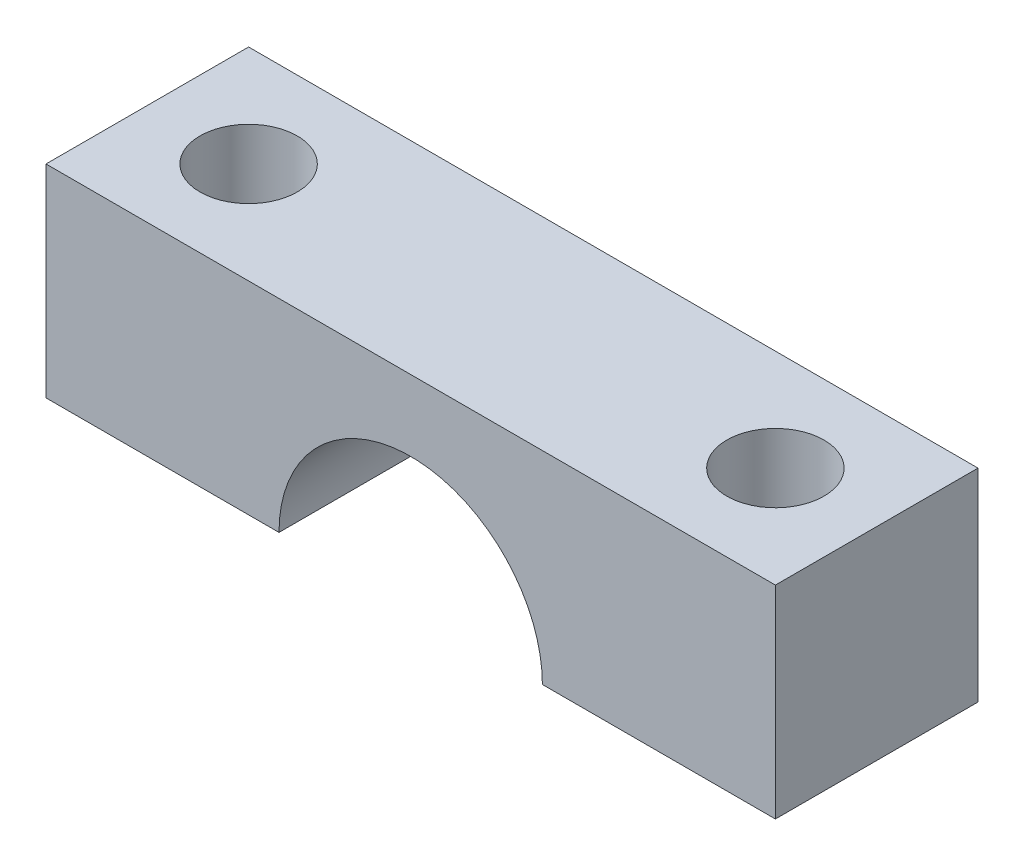
SolidWorks part; units mm, degrees
ref_plane "Front Plane" through (0, 0, 0) normal (0, 0, 1) x (1, 0, 0)
ref_plane "Top Plane" through (0, 0, 0) normal (0, 1, 0) x (1, 0, 0)
ref_plane "Right Plane" through (0, 0, 0) normal (1, 0, 0) x (0, 0, -1)
sketch "Sketch1" plane through (0, 0, 0) normal (0, 0, 1) x (1, 0, 0)
  line L0 (0, 0) -> (0, 5) construction
  line L1 (3.25, 0) -> (9, 0)
  line L2 (9, 0) -> (9, 5)
  line L3 (9, 5) -> (-9, 5)
  line L4 (-9, 0) -> (-9, 5)
  line L5 (-3.25, 0) -> (-9, 0)
  arc A0 (3.25, 0) -> (-3.25, 0) centre (0, 0) ccw
  dimension "D3" = 3.25
  dimension "D1" = 18
  dimension "D2" = 5
extrude "Boss-Extrude1" add sketch "Sketch1" along normal blind 5
sketch "Sketch2" plane through (0, 0, 0) normal (0, 1, 0) x (1, 0, 0)
  line L0 (0, 0) -> (0, -5) construction
  line L1 (9, 0) -> (-9, 0) construction
  line L2 (9, -5) -> (-9, -5) construction
  line L3 (-9, -5) -> (-9, 0) construction
  circle A0 centre (-6.5, -2.5) radius 1.2
  circle A1 centre (6.5, -2.5) radius 1.2
  dimension "D1" = 2.5
  dimension "D2" = 2.5
  dimension "D3" = 2.4
extrude "Cut-Extrude1" cut sketch "Sketch2" along normal through all
